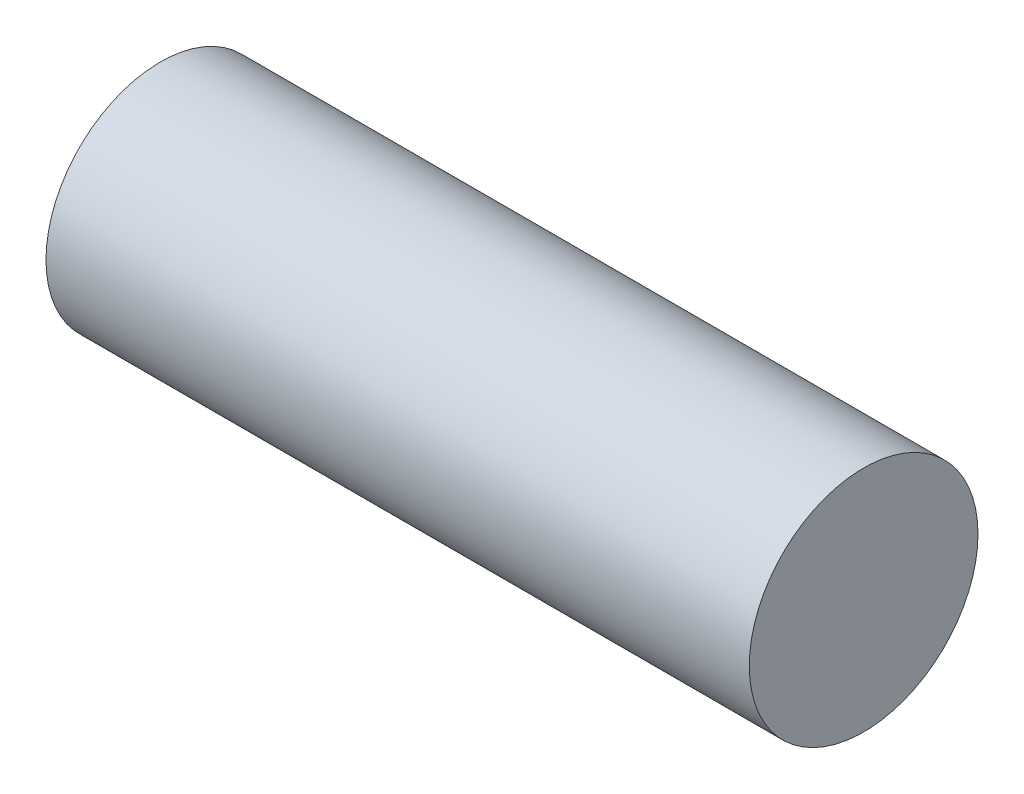
SolidWorks part; units mm, degrees
ref_plane "Front Plane" through (0, 0, 0) normal (0, 0, 1) x (1, 0, 0)
ref_plane "Top Plane" through (0, 0, 0) normal (0, 1, 0) x (1, 0, 0)
ref_plane "Right Plane" through (0, 0, 0) normal (1, 0, 0) x (0, 0, -1)
sketch "Pin_Outer Sketch" plane through (0, 0, 0) normal (0, 0, 1) x (1, 0, 0)
  line L0 (-1000, 0) -> (1000, 0) construction
  line L1 (80.5, 0) -> (80.5, 3)
  line L2 (80.5, 3) -> (99.25, 3)
  line L3 (99.25, 3) -> (99.25, 0)
  line L4 (99.25, 0) -> (80.5, 0)
revolve "Pin_Outer" add sketch "Pin_Outer Sketch" angle 360 about L0
ref_axis "Engine Axis" through (99.8725, 0, 0) along (-1, 0, 0)
sketch "Clear The Wall Sketch" plane through (0, 0, 0) normal (0, 0, 1) x (1, 0, 0)
  line L0 (-1000, 0) -> (1000, 0) construction
  line L1 (98.95, 0) -> (100.25, 0)
  line L2 (100.25, 0) -> (100.25, 4)
  line L3 (100.25, 4) -> (98.95, 4)
  line L4 (98.95, 4) -> (98.95, 0)
revolve "Clear The Wall" cut sketch "Clear The Wall Sketch" angle 360 about L0
